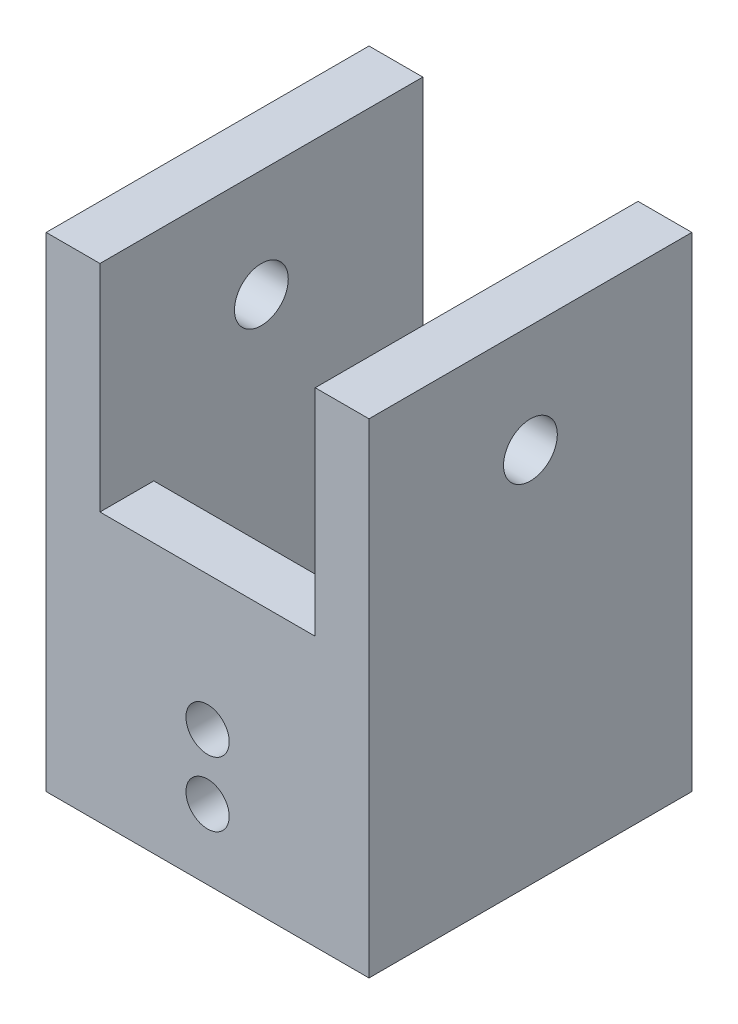
SolidWorks part; units mm, degrees
ref_plane "Front" through (0, 0, 0) normal (0, 0, 1) x (1, 0, 0)
ref_plane "Top" through (0, 0, 0) normal (0, 1, 0) x (1, 0, 0)
ref_plane "Right" through (0, 0, 0) normal (1, 0, 0) x (0, 0, -1)
sketch "Sketch1" plane through (0, 0, 0) normal (0, 1, 0) x (1, 0, 0)
  line L0 (6.35, 6.35) -> (6.35, 31.75)
  line L1 (0, 0) -> (38.1, 0)
  line L2 (0, 0) -> (0, 38.1)
  line L3 (0, 38.1) -> (38.1, 38.1)
  line L4 (38.1, 0) -> (38.1, 38.1)
  line L5 (6.35, 31.75) -> (31.75, 31.75)
  line L6 (31.75, 6.35) -> (31.75, 31.75)
  line L7 (6.35, 6.35) -> (31.75, 6.35)
  dimension "D1" = 38.1
  dimension "D2" = 6.35
extrude "Boss-Extrude1" add sketch "Sketch1" along normal blind 57.15
sketch "Sketch2" plane through (0, 0, 0) normal (0, 0, 1) x (1, 0, 0)
  line L5 (6.35, 31.75) -> (31.75, 31.75)
  line L6 (6.35, 31.75) -> (6.35, 57.15)
  line L7 (6.35, 57.15) -> (31.75, 57.15)
  line L8 (31.75, 31.75) -> (31.75, 57.15)
  line L11 (0, 57.15) -> (38.1, 57.15) construction
  dimension "D1" = 25.4
extrude "Cut-Extrude1" cut sketch "Sketch2" against normal through all
sketch "Sketch3" plane through (38.1, 0, 0) normal (1, 0, 0) x (0, 0, -1)
  line L0 (0, 57.15) -> (38.1, 57.15) construction
  circle A0 centre (19.05, 44.45) radius 3.175
  point P4 (19.05, 57.15)
  dimension "D2" = 6.35
  dimension "D1" = 12.7
extrude "Cut-Extrude2" cut sketch "Sketch3" against normal through all and the other way through all
sketch "Sketch6" plane through (0, 0, -6.35) normal (0, 0, -1) x (-1, 0, 0)
  line L0 (-31.75, 31.75) -> (-6.35, 31.75) construction
  line L2 (-19.05, 15.875) -> (-19.05, 31.75) construction
  point P0 (-19.05, 15.875)
  point P3 (-19.05, 8.255)
  dimension "D1" = 15.875
  dimension "D2" = 7.62
hole_wizard "1/4-20 Tapped Hole1" positions "Sketch6" profile "Sketch5" tap size "1/4-20" standard "ANSI Inch"
sketch "Sketch5" plane through (19.05, 15.875, -6.35) normal (1, 0, 0) x (0, 1, 0)
  line L0 (0, 0) -> (0, 18.0438)
  line L1 (0, 18.0438) -> (2.5527, 16.51)
  line L2 (2.5527, 16.51) -> (2.5527, 0)
  line L5 (2.5527, 0) -> (0, 0)
  line L10 (0, 18.0438) -> (-2.5527, 16.51) construction
  line L11 (0, -6.35) -> (0, 107.95) construction
  dimension "Tap Drill Dia." = 5.1054
  dimension "Tap Drill Depth" = 16.51
  dimension "Drill Angle" = 118
cosmetic thread "Hole Thread1" parameters "D1"=12.7, "D2"=6.35
cosmetic thread "Hole Thread2" parameters "D1"=12.7, "D2"=6.35
sketch "Sketch7" plane through (0, 0, -38.1) normal (0, 0, -1) x (-1, 0, 0)
  circle A0 centre (-19.05, 15.875) radius 3.175
  circle A1 centre (-19.05, 8.255) radius 3.175
  circle A2 centre (-19.05, 15.875) radius 2.5527 construction
  circle A3 centre (-19.05, 8.255) radius 2.5527 construction
  dimension "D1" = 6.35
extrude "Cut-Extrude3" cut sketch "Sketch7" against normal blind 6.35
